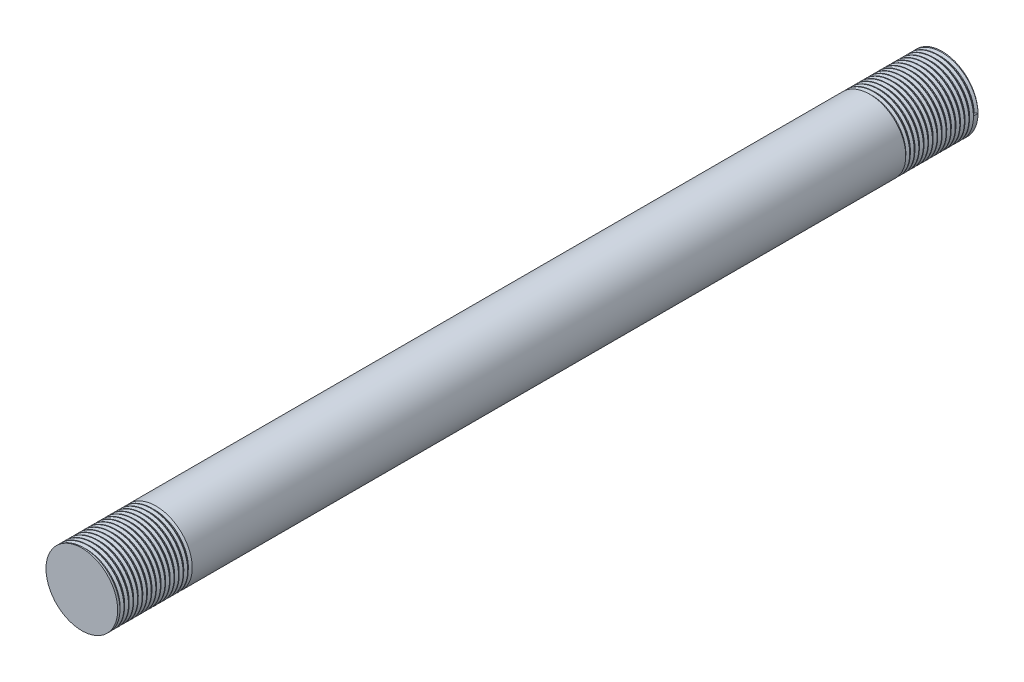
SolidWorks part; units mm, degrees
ref_plane "Front Plane" through (0, 0, 0) normal (0, 0, 1) x (1, 0, 0)
ref_plane "Top Plane" through (0, 0, 0) normal (0, 1, 0) x (1, 0, 0)
ref_plane "Right Plane" through (0, 0, 0) normal (1, 0, 0) x (0, 0, -1)
sketch "Sketch1" plane through (0, 0, 0) normal (0, 0, 1) x (1, 0, 0)
  circle A0 centre (0, 0) radius 2.5
extrude "Boss-Extrude1" add sketch "Sketch1" along normal blind 60
thread "Thread1" pitch 0.3175 method cut profile "Thread Profile1" start angle 0, offset 0, length 5, pitch 0.3175, diameter 5
ref_plane "Plane1" through (-2.5, 0, 60) normal (0, -1, 0) x (-1, 0, 0)
sketch "Thread Profile1" plane through (-2.5, 0, 60) normal (0, -1, 0) x (-1, 0, 0)
  line L0 (0, 0) -> (0, 0.3175) construction
  line L11 (0, 0) -> (0, 0.2778)
  line L12 (0, 0.2778) -> (-0.1719, 0.1786)
  line L13 (-0.1719, 0.1786) -> (-0.1719, 0.0992)
  line L15 (-0.1719, 0.0992) -> (0, 0)
  line L17 (-0.1719, 0.1389) -> (0, 0.1389) construction
  point P2 (0, 0)
  dimension "Pitch" = 0.3175
  dimension "Profile_Angle" = 60
  dimension "Profile_Land" = 0.0794
  dimension "Profile_Height" = 0.1719
ref_plane "Plane2" through (0, 0, 20) normal (0, 0, 1) x (1, 0, 0)
thread "Thread2" pitch 0.3175 method cut profile "Thread Profile2" start angle 0, offset 0, length 5, pitch 0.3175, diameter 5
ref_plane "Plane3" through (2.5, 0, 0) normal (0, -1, 0) x (1, 0, 0)
sketch "Thread Profile2" plane through (2.5, 0, 0) normal (0, -1, 0) x (1, 0, 0)
  line L0 (0, 0) -> (0, 0.3175) construction
  line L11 (0, 0) -> (0, 0.2778)
  line L12 (0, 0.2778) -> (-0.1719, 0.1786)
  line L13 (-0.1719, 0.1786) -> (-0.1719, 0.0992)
  line L15 (-0.1719, 0.0992) -> (0, 0)
  line L17 (-0.1719, 0.1389) -> (0, 0.1389) construction
  point P2 (0, 0)
  dimension "Pitch" = 0.3175
  dimension "Profile_Angle" = 60
  dimension "Profile_Land" = 0.0794
  dimension "Profile_Height" = 0.1719
